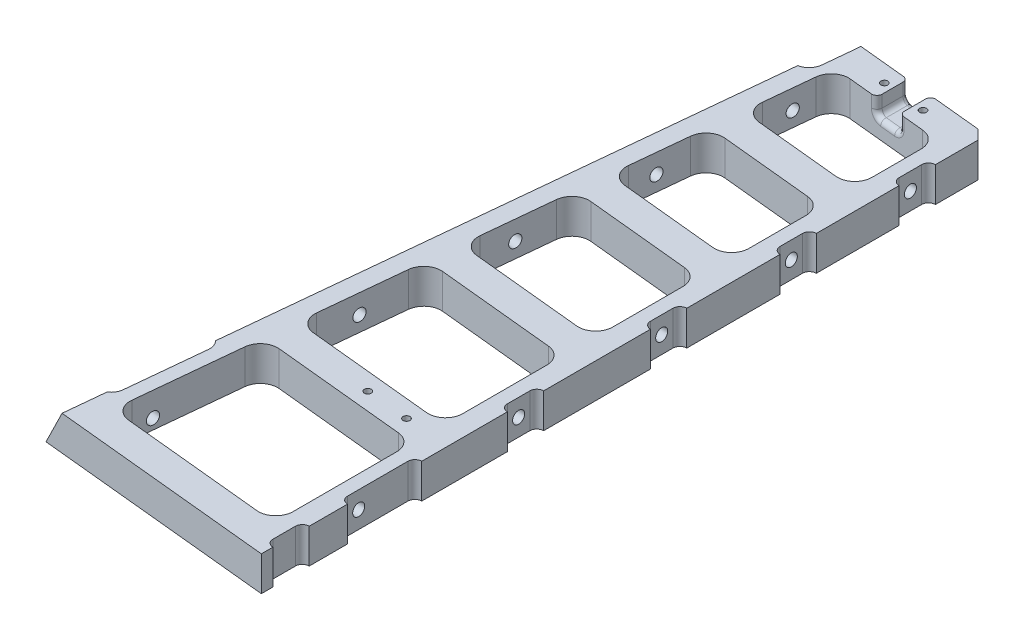
SolidWorks part; units mm, degrees
material "PE High Density"
ref_plane "Front Plane" through (0, 0, 0) normal (0, 0, 1) x (1, 0, 0)
ref_plane "Top Plane" through (0, 0, 0) normal (0, 1, 0) x (1, 0, 0)
ref_plane "Right Plane" through (0, 0, 0) normal (1, 0, 0) x (0, 0, -1)
sketch "Sketch1" plane through (0, 0, 0) normal (0, 1, 0) x (1, 0, 0)
  line L0 (-138.5293, 13.8271) -> (0, 0)
  line L1 (0, 0) -> (0, 420)
  line L2 (0, 420) -> (-97.0213, 429.684)
  line L3 (-97.0213, 429.684) -> (-138.5293, 13.8271)
  dimension "D1" = 5.7
  dimension "D2" = 139.2177
  dimension "D3" = 97.0213
  dimension "D4" = 420
extrude "Boss-Extrude1" add sketch "Sketch1" along normal blind 20
sketch "Sketch3" plane through (41.508, 0, -415.8569) normal (0.0993, 0, -0.9951) x (-0.9951, 0, -0.0993)
  line L0 (139.2177, 0) -> (128.8374, 20)
  line L1 (41.7143, 20) -> (139.2177, 20) construction
  line L2 (128.8374, 20) -> (139.2177, 20)
  line L3 (139.2177, 20) -> (139.2177, 0)
  line L5 (41.7143, 0) -> (139.2177, 0) construction
  dimension "D1" = 62.57
extrude "Cut-Extrude1" cut sketch "Sketch3" against normal through all
sketch "Sketch4" plane through (0, 20, 0) normal (0, 1, 0) x (1, 0, 0)
  line L0 (0, 420) -> (-86.6923, 428.653) construction
  line L1 (0, 0) -> (0, 420) construction
  line L2 (-128.2004, 12.7961) -> (-86.6923, 428.653) construction
  line L4 (-46.654, 360.05) -> (-47.7492, 338.05) construction
  line L5 (-24.4597, 381.1669) -> (-24.4597, 65.3086) construction
  line L6 (-50.1864, 289.0944) -> (-51.2816, 267.0944) construction
  line L7 (-41.3151, 424.1238) -> (-43.5028, 402.2055) construction
  line L8 (-54.0884, 210.7135) -> (-55.1836, 188.7135) construction
  line L9 (-64.9888, 28.6234) -> (-67.1765, 6.7051) construction
  line L10 (-58.3988, 124.1304) -> (-59.494, 102.1304) construction
  line L11 (-128.2004, 12.7961) -> (0, 0) construction
  circle A0 centre (-45.6027, 381.1669) radius 21.1431
  circle A1 centre (-48.9678, 313.5722) radius 24.5081
  circle A2 centre (-52.685, 238.9039) radius 28.2253
  circle A3 centre (-56.7912, 156.422) radius 32.3315
  circle A4 centre (-45.6027, 381.1669) radius 45.6027 construction
  circle A5 centre (-48.9678, 313.5722) radius 48.9678 construction
  circle A6 centre (-52.685, 238.9039) radius 52.685 construction
  circle A7 centre (-56.7912, 156.422) radius 56.7912 construction
  circle A8 centre (-61.3271, 65.3086) radius 61.3271 construction
  circle A9 centre (-61.3271, 65.3086) radius 36.8674
  dimension "D1" = 22
extrude "lightening holes" cut sketch "Sketch4" against normal through all
sketch "Sketch6" plane through (0, 20, 0) normal (0, 1, 0) x (1, 0, 0)
  line L0 (-12, 403.1083) -> (-77.6075, 409.6568)
  line L1 (-12, 403.1083) -> (-12, 354.5827)
  line L2 (-77.6075, 409.6568) -> (-82.4032, 361.6099)
  line L3 (-12, 354.5827) -> (-82.4032, 361.6099)
  line L4 (-12, 403.1083) -> (-82.4032, 361.6099) construction
  line L5 (-77.6075, 409.6568) -> (-12, 354.5827) construction
  line L6 (-12, 336.4902) -> (-84.1913, 343.6958)
  line L7 (-12, 336.4902) -> (-12, 283.2749)
  line L8 (-84.1913, 343.6958) -> (-89.4505, 291.0055)
  line L9 (-12, 283.2749) -> (-89.4505, 291.0055)
  line L10 (-12, 336.4902) -> (-89.4505, 291.0055) construction
  line L11 (-84.1913, 343.6958) -> (-12, 283.2749) construction
  line L12 (-12, 265.1824) -> (-91.2385, 273.0914)
  line L13 (-12, 265.1824) -> (-12, 204.5041)
  line L14 (-91.2385, 273.0914) -> (-97.2353, 213.0117)
  line L15 (-12, 204.5041) -> (-97.2353, 213.0117)
  line L16 (-12, 265.1824) -> (-97.2353, 213.0117) construction
  line L17 (-91.2385, 273.0914) -> (-12, 204.5041) construction
  line L18 (-12, 186.4116) -> (-99.0233, 195.0977)
  line L19 (-12, 186.4116) -> (-12, 117.5687)
  line L20 (-99.0233, 195.0977) -> (-105.827, 126.9338)
  line L21 (-12, 117.5687) -> (-105.827, 126.9338)
  line L22 (-12, 186.4116) -> (-105.827, 126.9338) construction
  line L23 (-99.0233, 195.0977) -> (-12, 117.5687) construction
  line L24 (-12, 19.2903) -> (-115.5397, 29.6249)
  line L25 (-12, 19.2903) -> (-12, 99.4762)
  line L26 (-115.5397, 29.6249) -> (-107.6151, 109.0198)
  line L27 (-12, 99.4762) -> (-107.6151, 109.0198)
  line L28 (-12, 19.2903) -> (-107.6151, 109.0198) construction
  line L29 (-115.5397, 29.6249) -> (-12, 99.4762) construction
  line L30 (0, 0) -> (0, 420) construction
  line L31 (-46.654, 360.05) -> (-47.7492, 338.05) construction
  line L32 (-128.2004, 12.7961) -> (-86.6923, 428.653) construction
  line L33 (0, 420) -> (-86.6923, 428.653) construction
  line L34 (-43.3462, 424.3265) -> (-44.8037, 406.3826) construction
  line L35 (-50.1803, 289.0941) -> (-51.2701, 267.0938) construction
  line L36 (-46.3076, 358.007) -> (-48.0956, 340.093) construction
  line L37 (-128.2004, 12.7961) -> (0, 0) construction
  line L38 (-49.8312, 287.051) -> (-51.6193, 269.1369) construction
  line L39 (-54.0884, 210.7135) -> (-55.1836, 188.7135) construction
  line L40 (-53.742, 208.6705) -> (-55.53, 190.7565) construction
  line L41 (-64.1002, 6.398) -> (-62.3121, 24.3121) construction
  line L42 (-55.8972, 121.9502) -> (-57.6852, 104.0361) construction
  line L43 (-56.7912, 124.0904) -> (-56.7912, 101.8959) construction
  circle A0 centre (-48.9678, 313.5722) radius 24.5081 construction
  circle A1 centre (-45.6027, 381.1669) radius 21.1431 construction
  circle A5 centre (-52.685, 238.9039) radius 28.2253 construction
  circle A6 centre (-56.7912, 156.422) radius 32.3315 construction
  circle A7 centre (-61.3271, 65.3086) radius 36.8674 construction
  point P1 (-45.9604, 383.0907)
  point P2 (-49.3642, 314.5471)
  point P3 (-53.0638, 240.0481)
  point P8 (-57.1486, 157.7915)
  point P13 (-61.7099, 65.9403)
  point P54 (-54.636, 199.7135)
  point P59 (-56.7912, 112.9932)
  point P60 (-50.7252, 278.0939)
  point P61 (-47.2016, 349.05)
  point P62 (-56.7912, 156.422)
  point P63 (-61.3271, 65.3086)
  point P65 (-52.685, 238.9039)
  point P67 (-48.9678, 313.5722)
  point P69 (-45.6027, 381.1669)
  dimension "D1" = 12
  dimension "D2" = 18
extrude "Cut-Extrude3" cut sketch "Sketch6" against normal through all
fillet "Fillet2" radius 10 20 edges at (-82.4032, 10, -361.6099) (-89.4505, 10, -291.0055) (-105.827, 10, -126.9338) (-97.2353, 10, -213.0117) (-115.5397, 10, -29.6249) (-107.6151, 10, -109.0198) (-99.0233, 10, -195.0977) (-91.2385, 10, -273.0914) (-84.1913, 10, -343.6958) (-77.6075, 10, -409.6568) (-12, 10, -99.4762) (-12, 10, -19.2903) (-12, 10, -117.5687) (-12, 10, -204.5041) (-12, 10, -283.2749) (-12, 10, -354.5827) (-12, 10, -186.4116) (-12, 10, -265.1824) (-12, 10, -336.4902) (-12, 10, -403.1083)
sketch "Sketch7" plane through (0, 20, 0) normal (0, 1, 0) x (1, 0, 0)
  line L0 (-91.2319, 383.172) -> (-101.1725, 388.0947) construction
  line L1 (0, 386.3436) -> (0, 373.3436) construction
  line L2 (0, 0) -> (0, 420) construction
  line L3 (4, 386.3436) -> (4, 373.3436)
  line L4 (-4, 386.3436) -> (-4, 373.3436)
  line L5 (-95.5566, 392.1012) -> (-96.8478, 379.1655) construction
  line L6 (-90.9723, 400.0068) -> (-93.221, 377.4784)
  line L7 (-125.9159, 96.0575) -> (-148.6502, 101.4362)
  line L8 (-102.3721, 323.8185) -> (-103.6633, 310.8828) construction
  line L9 (-98.3919, 323.4212) -> (-99.6831, 310.4855)
  line L10 (-97.2451, 375.1853) -> (-103.4529, 375.8049)
  line L11 (-109.7882, 249.5194) -> (-111.0793, 236.5837) construction
  line L12 (-105.808, 249.1222) -> (-107.0991, 236.1864)
  line L13 (-102.3721, 327.8185) -> (-109.3909, 327.8185)
  line L14 (-117.9764, 167.4836) -> (-119.2676, 154.5479) construction
  line L15 (-113.9962, 167.0864) -> (-115.2874, 154.1506)
  line L16 (-109.3909, 253.4997) -> (-116.8955, 254.2487)
  line L17 (-125.9159, 87.9407) -> (-130.3853, 43.1632) construction
  line L18 (-117.8392, 87.1346) -> (-122.3086, 42.3571)
  line L19 (-86.896, 434.942) -> (-97.2743, 437.7071)
  line L20 (0, 66.8813) -> (0, 53.8813) construction
  line L21 (4, 66.8813) -> (4, 53.8813)
  line L22 (-4, 66.8813) -> (-4, 53.8813)
  line L23 (0, 159.4883) -> (0, 146.4883) construction
  line L24 (4, 159.4883) -> (4, 146.4883)
  line L25 (-4, 159.4883) -> (-4, 146.4883)
  line L26 (0, 242.3414) -> (0, 229.3414) construction
  line L27 (4, 242.3414) -> (4, 229.3414)
  line L28 (-4, 242.3414) -> (-4, 229.3414)
  line L29 (0, 317.3807) -> (0, 304.3807) construction
  line L30 (4, 317.3807) -> (4, 304.3807)
  line L31 (-4, 317.3807) -> (-4, 304.3807)
  line L32 (-12, 379.8436) -> (0, 379.8436) construction
  line L33 (-12, 365.6305) -> (-12, 394.0568) construction
  line L34 (-128.2004, 12.7961) -> (-86.6923, 428.653) construction
  line L35 (0, 310.8807) -> (-12, 310.8807) construction
  line L36 (-12, 294.3227) -> (-12, 327.4386) construction
  line L37 (-97.0213, 429.684) -> (-138.5293, 13.8271) construction
  line L38 (-12, 215.5519) -> (-12, 256.1308) construction
  line L39 (-12, 235.8414) -> (0, 235.8414) construction
  line L40 (0, 10.7314) -> (0, 23.7314) construction
  line L41 (0, 152.9883) -> (-12, 152.9883) construction
  line L42 (-12, 128.6165) -> (-12, 177.3601) construction
  line L43 (-4, 10.7314) -> (-4, 23.7314)
  line L44 (0, 60.3813) -> (-12, 60.3813) construction
  line L45 (-12, 30.3381) -> (-12, 90.4246) construction
  line L46 (4, 10.7314) -> (4, 23.7314)
  line L47 (-97.0213, 429.684) -> (-138.5293, 13.8271) construction
  line L48 (-111.6102, 65.552) -> (-128.1506, 65.552) construction
  line L49 (0, 17.2314) -> (10, 17.2314) construction
  line L50 (-100.0165, 185.1471) -> (-104.8338, 136.8844) construction
  line L51 (-102.4252, 161.0158) -> (-118.622, 161.0158) construction
  line L52 (-148.6502, 101.4362) -> (-151.0634, 35.0465)
  line L53 (-92.2317, 263.1409) -> (-96.2421, 222.9623) construction
  line L54 (-94.2369, 243.0516) -> (-110.4338, 243.0516) construction
  line L55 (-128.2004, 12.7961) -> (0, 0) construction
  line L56 (-85.1845, 333.7453) -> (-88.4573, 300.956) construction
  line L57 (-86.8209, 317.3506) -> (-103.0177, 317.3506) construction
  line L58 (-108.6083, 99.0692) -> (-114.5465, 39.5755) construction
  line L59 (-78.6007, 399.7063) -> (-81.41, 371.5604) construction
  line L60 (-80.0054, 385.6333) -> (-96.2022, 385.6333) construction
  line L61 (-90.902, 408.1101) -> (-88.9556, 427.2117) construction
  line L63 (-82.9022, 407.3116) -> (-80.9952, 426.4171)
  line L66 (-117.5792, 171.4639) -> (-125.9159, 172.296)
  line L67 (-125.9159, 172.296) -> (-128.0261, 151.1538)
  line L68 (-128.0261, 151.1538) -> (-119.6649, 150.5677)
  line L69 (-116.8955, 254.2487) -> (-119.0245, 232.9183)
  line L70 (-119.0245, 232.9183) -> (-111.4766, 232.6035)
  line L71 (-109.3909, 327.8185) -> (-111.4766, 307.4085)
  line L72 (-111.4766, 307.4085) -> (-104.0606, 306.9026)
  line L73 (-151.0634, 35.0465) -> (-130.3853, 35.0465)
  line L74 (-97.2743, 437.7071) -> (-103.4529, 375.8049)
  arc A0 (4, 386.3436) -> (-4, 386.3436) centre (0, 386.3436) ccw
  arc A1 (-4, 373.3436) -> (4, 373.3436) centre (0, 373.3436) ccw
  arc A3 (-97.2451, 375.1853) -> (-93.221, 377.4784) centre (-96.8478, 379.1655) ccw
  arc A4 (-98.3919, 323.4212) -> (-102.3721, 327.8185) centre (-102.3721, 323.8185) ccw
  arc A5 (-104.0606, 306.9026) -> (-99.6831, 310.4855) centre (-103.6633, 310.8828) ccw
  arc A6 (-105.808, 249.1222) -> (-109.3909, 253.4997) centre (-109.7882, 249.5194) ccw
  arc A7 (-111.4766, 232.6035) -> (-107.0991, 236.1864) centre (-111.0793, 236.5837) ccw
  arc A8 (-113.9962, 167.0864) -> (-117.5792, 171.4639) centre (-117.9764, 167.4836) ccw
  arc A9 (-119.6649, 150.5677) -> (-115.2874, 154.1506) centre (-119.2676, 154.5479) ccw
  arc A10 (-117.8392, 87.1346) -> (-125.9159, 96.0575) centre (-125.9159, 87.9407) ccw
  arc A11 (-130.3853, 35.0465) -> (-122.3086, 42.3571) centre (-130.3853, 43.1632) ccw
  arc A12 (4, 66.8813) -> (-4, 66.8813) centre (0, 66.8813) ccw
  arc A13 (-4, 53.8813) -> (4, 53.8813) centre (0, 53.8813) ccw
  arc A14 (4, 159.4883) -> (-4, 159.4883) centre (0, 159.4883) ccw
  arc A15 (-4, 146.4883) -> (4, 146.4883) centre (0, 146.4883) ccw
  arc A16 (4, 242.3414) -> (-4, 242.3414) centre (0, 242.3414) ccw
  arc A17 (-4, 229.3414) -> (4, 229.3414) centre (0, 229.3414) ccw
  arc A18 (4, 317.3807) -> (-4, 317.3807) centre (0, 317.3807) ccw
  arc A19 (-4, 304.3807) -> (4, 304.3807) centre (0, 304.3807) ccw
  arc A20 (-4, 10.7314) -> (4, 10.7314) centre (0, 10.7314) ccw
  arc A21 (4, 23.7314) -> (-4, 23.7314) centre (0, 23.7314) ccw
  arc A22 (-90.902, 400.0705) -> (-82.9022, 407.3116) centre (-90.902, 408.1101) ccw
  arc A23 (-80.9952, 426.4171) -> (-86.896, 434.942) centre (-88.9556, 427.2117) ccw
  arc A24 (-90.9723, 400.0068) -> (-90.902, 400.0705) centre (-90.902, 399.9998) cw
  point P4 (0, 379.8436)
  point P10 (-96.2022, 385.6333)
  point P17 (-103.0177, 317.3506)
  point P24 (-110.4338, 243.0516)
  point P31 (-118.622, 161.0158)
  point P38 (-128.1506, 65.552)
  point P45 (0, 60.3813)
  point P52 (0, 152.9883)
  point P59 (0, 235.8414)
  point P66 (0, 310.8807)
  point P120 (0, 17.2314)
  point P132 (-88.0331, 415.2198)
  dimension "D1" = 4
  dimension "D9" = 8
  dimension "D2" = 13
  dimension "D3" = 17.1462
  dimension "D4" = 8
  dimension "D5" = 45
  dimension "D6" = 30
extrude "Cut-Extrude4" cut sketch "Sketch7" against normal through all
sketch "Sketch8" plane through (-4, 0, 0) normal (1, 0, 0) x (0, 0, -1)
  line L0 (60.3813, 20) -> (60.3813, 0) construction
  line L1 (66.8813, 20) -> (53.8813, 20) construction
  line L3 (60.3813, 0) -> (152.9883, 0) construction
  line L5 (152.9883, 0) -> (152.9883, 20) construction
  line L6 (159.4883, 20) -> (146.4883, 20) construction
  line L8 (242.3414, 20) -> (229.3414, 20) construction
  line L9 (235.8414, 20) -> (235.8414, 0) construction
  line L13 (310.8807, 0) -> (310.8807, 20) construction
  line L14 (317.3807, 20) -> (304.3807, 20) construction
  line L15 (310.8807, 20) -> (379.8436, 20) construction
  line L16 (386.3436, 20) -> (373.3436, 20) construction
  line L17 (379.8436, 20) -> (379.8436, 0) construction
  line L19 (390.3436, 0) -> (420, 0) construction
  circle A0 centre (379.8436, 10) radius 3.5
  circle A1 centre (310.8807, 10) radius 3.5
  circle A2 centre (235.8414, 10) radius 3.5
  circle A3 centre (152.9883, 10) radius 3.5
  circle A4 centre (60.3813, 10) radius 3.5
  dimension "D1" = 7
extrude "Cut-Extrude5" cut sketch "Sketch8" against normal blind 15
sketch "Sketch9" plane through (-129.6071, 0, -12.9365) normal (-0.9951, 0, -0.0993) x (-0.0993, 0, 0.9951)
  line L0 (-377.6735, 17.2761) -> (-377.6735, 0) construction
  line L1 (-366.3533, 17.2761) -> (-388.9937, 17.2761) construction
  line L2 (-87.7925, 0) -> (-28.0031, 0) construction
  line L3 (-305.5498, 0) -> (-305.5498, 17.7069) construction
  line L4 (-299.0498, 17.7069) -> (-312.0498, 17.7069) construction
  line L5 (-366.3533, 0) -> (-388.9937, 0) construction
  line L6 (-224.3816, 17.7069) -> (-237.3816, 17.7069) construction
  line L7 (-230.8816, 17.7069) -> (-230.8816, 0) construction
  line L9 (-299.0498, 0) -> (-312.0498, 0) construction
  line L10 (-39.1577, 17) -> (-39.1577, -5) construction
  line L11 (-148.4381, 17.7069) -> (-148.4381, 0) construction
  line L12 (-141.9381, 17.7069) -> (-154.9381, 17.7069) construction
  line L13 (-224.3816, 0) -> (-237.3816, 0) construction
  line L14 (-141.9381, 0) -> (-154.9381, 0) construction
  circle A0 centre (-377.6735, 8.6381) radius 3.5
  circle A1 centre (-305.5498, 8.8535) radius 3.5
  circle A2 centre (-230.8816, 8.8535) radius 3.5
  circle A3 centre (-148.4381, 8.8535) radius 3.5
  circle A4 centre (-39.1577, 6) radius 3.5
  dimension "D1" = 7
  dimension "D3" = 6
extrude "Cut-Extrude6" cut sketch "Sketch9" against normal blind 15
sketch "Sketch10" plane through (0, 20, 0) normal (0, 1, 0) x (1, 0, 0)
  line L0 (-35.8, 433.5941) -> (-35.8, 398.3945)
  line L1 (-35.8, 433.5941) -> (-50.8, 433.5941)
  line L2 (-35.8, 398.3945) -> (-50.8, 398.3945)
  line L3 (-50.8, 433.5941) -> (-50.8, 398.3945)
  line L4 (-35.8, 433.5941) -> (-50.8, 398.3945) construction
  line L5 (-35.8, 398.3945) -> (-50.8, 433.5941) construction
  line L6 (0, 0) -> (0, 6.7314) construction
  point P1 (-43.3, 415.9943)
  dimension "D1" = 43.3
  dimension "D2" = 15
extrude "Cut-Extrude7" cut sketch "Sketch10" against normal blind 10
sketch "Sketch12" plane through (0, 20, 0) normal (0, 1, 0) x (1, 0, 0)
  line L0 (-50.8, 416.0258) -> (-35.8, 414.5286) construction
  line L1 (-35.8, 405.4839) -> (-35.8, 423.5733) construction
  line L2 (-50.8, 425.0705) -> (-50.8, 406.9811) construction
  line L3 (-30.8618, 414.0357) -> (-55.7382, 416.5187) construction
  line L4 (-30.8618, 423.0804) -> (-30.8618, 404.991) construction
  line L5 (0, 420) -> (-35.8, 423.5733) construction
  line L6 (-21.0068, 404.0073) -> (-35.8, 405.4839) construction
  line L7 (-25.8618, 118.9523) -> (-25.8618, 100.8597) construction
  line L8 (-50.8, 406.9811) -> (-67.6569, 408.6636) construction
  line L9 (-56.6321, 407.5632) -> (-54.8443, 425.4742) construction
  line L10 (-50.8, 425.0705) -> (-81.0035, 428.0852) construction
  line L11 (-95.8764, 125.9407) -> (-22.9932, 118.6659) construction
  line L12 (-21.0068, 100.3752) -> (-97.6645, 108.0266) construction
  line L13 (-25.8618, 100.8597) -> (-52.6653, 103.5351) construction
  line L14 (-52.6653, 103.5351) -> (-48.8111, 121.2429) construction
  circle A0 centre (-30.8618, 414.0357) radius 2
  circle A1 centre (-55.7382, 416.5187) radius 2
  circle A2 centre (-25.8618, 109.906) radius 2
  circle A3 centre (-50.7382, 112.389) radius 2
  point P8 (-43.3, 415.2772)
  dimension "D1" = 4
  dimension "D2" = 25
  dimension "D3" = 25
  dimension "D4" = 5
extrude "Cut-Extrude8" cut sketch "Sketch12" against normal through all
fillet "Fillet3" radius 3 8 edges at (-35.8, 15, -405.4839) (-50.8, 15, -406.9811) (-50.8, 15, -425.0705) (-35.8, 10, -414.5286) (-43.3, 10, -406.2325) (-50.8, 10, -416.0258) (-43.3, 10, -424.3219) (-35.8, 15, -423.5733)
hole_wizard "Ø9.0 (9) Diameter Hole1" positions "Sketch15" profile "Sketch14" hole size "Ø9.0" standard "ISO"
sketch "Sketch15" plane through (0, 0, 0) normal (0, -1, 0) x (-1, 0, 0)
  point P0 (55.7382, 416.5187)
  point P3 (30.8618, 414.0357)
  point P6 (50.7382, 112.389)
  point P9 (25.8618, 109.906)
sketch "Sketch14" plane through (-55.7382, 0, -416.5187) normal (1, 0, 0) x (0, 0, -1)
  line L0 (0, 0) -> (0, 12.7039)
  line L1 (0, 12.7039) -> (4.5, 10)
  line L2 (4.5, 10) -> (4.5, 0)
  line L5 (4.5, 0) -> (0, 0)
  line L10 (0, 12.7039) -> (-4.5, 10) construction
  line L11 (0, -6.35) -> (0, 107.95) construction
  dimension "Hole Dia." = 9
  dimension "Hole Depth" = 10
  dimension "Drill Angle" = 118
chamfer "Chamfer1" distance 5 angle 45 1 edges at (0, 10, -420) first distance on face at (0, 10, -405.1718)
sketch "Sketch16" plane through (0, 20, 0) normal (0, 1, 0) x (1, 0, 0)
  line L0 (0, 53.8813) -> (0, 88.8813) construction
  line L1 (0, 70.8813) -> (0, 142.4883) construction
  line L2 (-4, 53.8813) -> (-4, 88.8813)
  line L3 (4, 53.8813) -> (4, 88.8813)
  arc A0 (-4, 53.8813) -> (4, 53.8813) centre (0, 53.8813) ccw
  arc A1 (4, 88.8813) -> (-4, 88.8813) centre (0, 88.8813) ccw
  arc A2 (-4, 53.8813) -> (0, 49.8813) centre (0, 53.8813) ccw construction
  point P4 (0, 71.3813)
  dimension "D1" = 35
extrude "Cut-Extrude9" cut sketch "Sketch16" against normal blind 20
